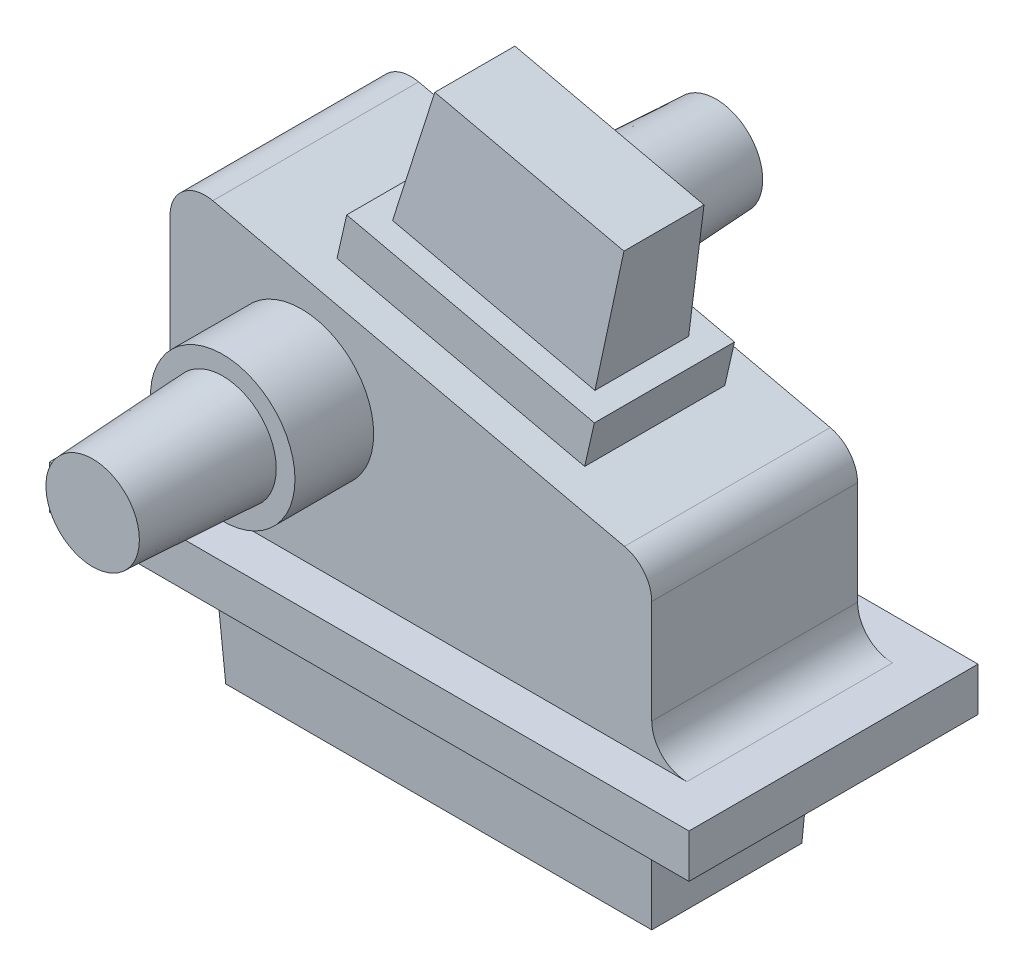
SolidWorks part; units mm, degrees
ref_plane "Front Plane" through (0, 0, 0) normal (0, 0, 1) x (1, 0, 0)
ref_plane "Top Plane" through (0, 0, 0) normal (0, 1, 0) x (1, 0, 0)
ref_plane "Right Plane" through (0, 0, 0) normal (1, 0, 0) x (0, 0, -1)
sketch "Sketch1" plane through (0, 0, 0) normal (0, 0, 1) x (1, 0, 0)
  line L0 (-73, 0) -> (73, 0)
  line L1 (73, 0) -> (73, 7)
  line L2 (73, 7) -> (63, 7)
  line L3 (55, 15) -> (55, 45)
  line L4 (55, 45) -> (-55, 70)
  line L5 (-55, 70) -> (-55, 15)
  line L6 (-63, 7) -> (-73, 7)
  line L7 (-73, 7) -> (-73, 0)
  line L8 (0, 150.8337) -> (0, -109.4097) construction
  arc A1 (-55, 15) -> (-63, 7) centre (-63, 15) cw
  arc A2 (63, 7) -> (55, 15) centre (63, 15) cw
  dimension "D4" = 110
  dimension "D5" = 8
  dimension "D8" = 55
  dimension "D1" = 45
  dimension "D2" = 7
  dimension "D3" = 7
  dimension "D6" = 73
  dimension "D7" = 146
  dimension "D9" = 70
extrude "Boss-Extrude1" add sketch "Sketch1" along normal mid plane 47
sketch "Sketch2" plane through (0, 0, 23.5) normal (0, 0, 1) x (1, 0, 0)
  line L0 (-73, 0) -> (73, 0) construction
  line L2 (-55, 70) -> (-55, 15) construction
  circle A1 centre (-25, 40) radius 16.5
  dimension "D2" = 33
  dimension "D3" = 40
  dimension "D4" = 30
extrude "Boss-Extrude2" add sketch "Sketch2" along normal blind 15 and the other way blind 62
sketch "Sketch3" plane through (0, 0, 0) normal (0, 0, 1) x (1, 0, 0)
  line L0 (-50, 0) -> (-50, 54.7538)
  line L1 (-73, 0) -> (73, 0) construction
  line L2 (-40.0597, 62.5149) -> (43.9403, 41.5149)
  line L3 (50, 33.7538) -> (50, 0)
  line L4 (50, 0) -> (-50, 0)
  arc A0 (50, 33.7538) -> (43.9403, 41.5149) centre (42, 33.7538) ccw
  arc A1 (-40.0597, 62.5149) -> (-50, 54.7538) centre (-42, 54.7538) ccw
  point P9 (50, 40)
  point P12 (-50, 65)
  dimension "D5" = 8
  dimension "D1" = 100
  dimension "D2" = 50
  dimension "D3" = 40
  dimension "D4" = 65
extrude "Cut-Extrude1" cut sketch "Sketch3" against normal mid plane 37
sketch "Sketch4" plane through (0, 0, 38.5) normal (0, 0, 1) x (1, 0, 0)
  circle A0 centre (-25, 40) radius 15
  dimension "D1" = 30
extrude "Cut-Extrude2" cut sketch "Sketch4" against normal through all
fillet "Fillet1" radius 8 2 edges at (-55, 70, 0) (55, 45, 0)
sketch "Sketch5" plane through (12.4263, 54.6758, 0) normal (0.2216, 0.9751, 0) x (0.9751, -0.2216, 0)
  line L0 (-43.5753, 0) -> (70.3693, 0) construction
  line L1 (0, -53.1002) -> (0, 65.858) construction
  line L3 (-37.736, 16) -> (20.264, 16)
  line L4 (-37.736, 16) -> (-37.736, -16)
  line L5 (-37.736, -16) -> (20.264, -16)
  line L6 (20.264, 16) -> (20.264, -16)
  line L9 (-72.736, -23.5) -> (-72.736, 23.5) construction
  point P5 (0, 0)
  point P6 (-37.736, 16)
  point P7 (-37.736, 14.9145)
  point P8 (0, 0)
  point P9 (0, 0)
  point P14 (20.264, -16)
  point P17 (20.264, 16)
  point P20 (-37.736, 16)
  dimension "D1" = 58
  dimension "D2" = 35
  dimension "D3" = 32
  dimension "D4" = 16
extrude "Boss-Extrude3" add sketch "Sketch5" along normal blind 7
sketch "Sketch6" plane through (13.9777, 61.5018, 0) normal (0.2216, 0.9751, 0) x (0.9751, -0.2216, 0)
  line L1 (-32.236, -10.5) -> (14.764, -10.5)
  line L2 (-32.236, -10.5) -> (-32.236, 10.5)
  line L3 (-32.236, 10.5) -> (14.764, 10.5)
  line L4 (14.764, -10.5) -> (14.764, 10.5)
  line L6 (-37.736, 16) -> (-37.736, -16) construction
  line L7 (20.264, -16) -> (20.264, 16) construction
  point P0 (0, 0)
  point P1 (-40.0175, -10.5)
  point P2 (-32.236, -17.9755)
  point P3 (-32.236, 21.2225)
  point P4 (-42.599, 10.5)
  point P12 (14.764, -10.5)
  point P17 (-32.236, -10.5)
  point P20 (21.3851, 10.5)
  point P21 (14.764, 18.885)
  point P22 (20.264, -10.5)
  point P23 (14.764, -16)
  dimension "D1" = 21
  dimension "D2" = 10.5
  dimension "D3" = 47
  dimension "D4" = 5.5
  dimension "D5" = 5.5
extrude "Cut-Extrude4" cut sketch "Sketch6" against normal up to surface (11.4326 mm away) up to face at (1.9403, 52.0149, 0)
sketch "Sketch7" plane through (0, 0, 0) normal (0, -1, 0) x (1, 0, 0)
  line L0 (73, -33) -> (73, 33)
  line L1 (73, 33) -> (-73, 33)
  line L2 (-73, 33) -> (-73, -33)
  line L3 (-73, -33) -> (73, -33)
  line L5 (-73, 23.5) -> (-73, -23.5) construction
  line L6 (50, -18.5) -> (-50, -18.5)
  line L7 (50, -18.5) -> (50, 18.5)
  line L8 (50, 18.5) -> (-50, 18.5)
  line L9 (-50, -18.5) -> (-50, 18.5)
  point P9 (0, 0)
  dimension "D1" = 33
  dimension "D2" = 66
extrude "Boss-Extrude5" add sketch "Sketch7" against normal blind 7
fillet "Fillet2" [suppressed] radius 7
fillet "Fillet3" [suppressed] radius 7
fillet "Fillet4" [suppressed] radius 7
fillet "Fillet5" [suppressed] radius 7
fillet "Fillet7" [suppressed] radius 7
fillet "Fillet8" [suppressed] radius 8
fillet "Fillet9" [suppressed] radius 7
scale "Scale1" bodies to scale 108 scale about centroid uniform scaling yes scale factor 1.01
other "Move Face1" face at (-10.0752, 40.1325, 38.885) face at (-10.0752, 40.1325, -18.685) face at (-10.0752, 40.1325, -38.885) face at (0.0248, -0.2675, 0) face at (-10.0752, 40.1325, 38.885) face at (5.5383, 63.8048, 0) offset 3 parameters "D1"=3
sketch "Sketch8" plane through (0, 0, 41.885) normal (0, 0, 1) x (1, 0, 0)
  circle A2 centre (-25.2252, 40.1325) radius 12.35
  circle A3 centre (-25.2252, 40.1325) radius 12.35
  dimension "D1" = 0.2
extrude "Boss-Extrude6" add sketch "Sketch8" along normal blind 30 draft 3 separate body
sketch "Sketch9" plane through (0, 0, -41.885) normal (0, 0, -1) x (-1, 0, 0)
  circle A2 centre (25.2252, 40.1325) radius 12.35
  circle A3 centre (25.2252, 40.1325) radius 12.35
  dimension "D1" = 0.2
extrude "Boss-Extrude7" add sketch "Sketch9" along normal blind 30 draft 3 separate body
sketch "Sketch11" plane through (0, -3.2675, 0) normal (0, -1, 0) x (1, 0, 0)
  line L35 (50.7248, -18.885) -> (50.7248, 18.885)
  line L36 (-50.6752, -18.885) -> (50.7248, -18.885)
  line L37 (-50.6752, 18.885) -> (-50.6752, -18.885)
  line L38 (50.7248, 18.885) -> (-50.6752, 18.885)
  line L39 (50.7248, -18.885) -> (50.7248, 18.885)
  line L40 (-50.6752, -18.885) -> (50.7248, -18.885)
  line L41 (-50.6752, 18.885) -> (-50.6752, -18.885)
  line L42 (50.7248, 18.885) -> (-50.6752, 18.885)
  dimension "D1" = 0.2
sketch "Sketch12" plane through (14.7257, 64.7932, 0) normal (0.2216, 0.9751, 0) x (0.9751, -0.2216, 0)
  line L18 (15.1951, -10.805) -> (15.1951, 10.805)
  line L19 (15.1951, 10.805) -> (-32.6749, 10.805)
  line L20 (-32.6749, -10.805) -> (15.1951, -10.805)
  line L21 (-32.6749, 10.805) -> (-32.6749, -10.805)
  line L22 (15.1951, -10.805) -> (15.1951, 10.805)
  line L23 (15.1951, 10.805) -> (-32.6749, 10.805)
  line L24 (-32.6749, -10.805) -> (15.1951, -10.805)
  line L25 (-32.6749, 10.805) -> (-32.6749, -10.805)
  dimension "D1" = 0.2
extrude "Boss-Extrude10" add sketch "Sketch12" along normal blind 30 draft 3
extrude "Boss-Extrude9" add sketch "Sketch11" along normal blind 30 draft 3 separate body
